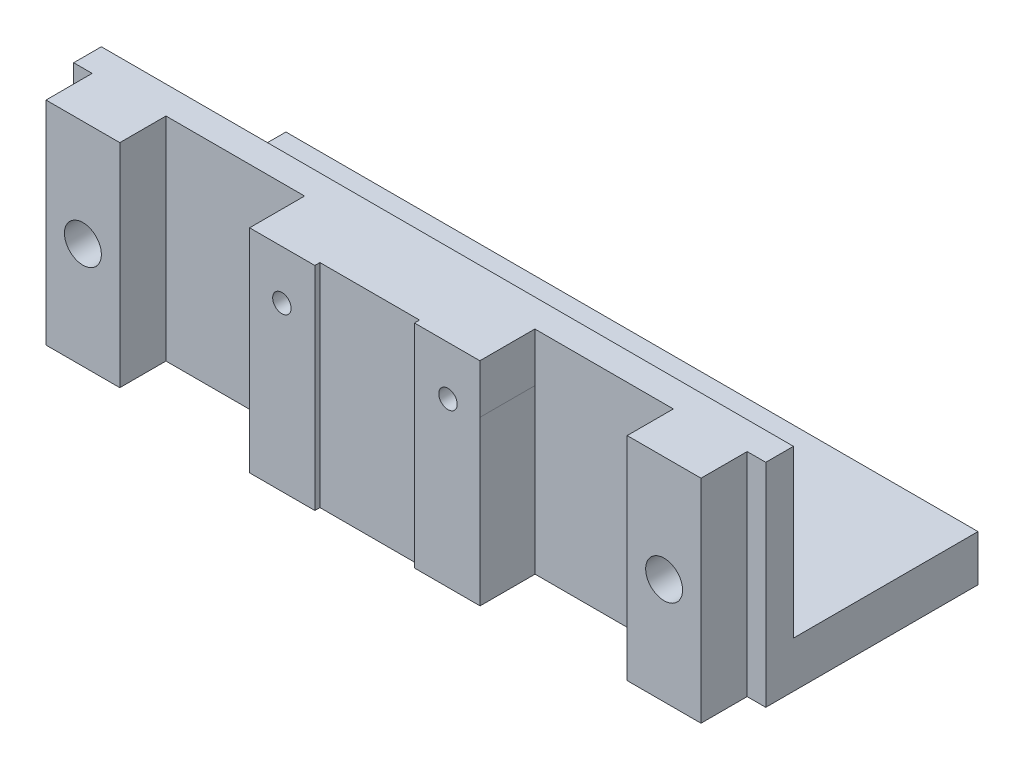
SolidWorks part; units mm, degrees
ref_plane "Front Plane" through (0, 0, 0) normal (0, 0, 1) x (1, 0, 0)
ref_plane "Top Plane" through (0, 0, 0) normal (0, 1, 0) x (1, 0, 0)
ref_plane "Right Plane" through (0, 0, 0) normal (1, 0, 0) x (0, 0, -1)
sketch "Sketch1" plane through (0, 0, 0) normal (0, 1, 0) x (1, 0, 0)
  line L1 (-25, -11.5) -> (25, -11.5)
  line L2 (-25, -11.5) -> (-25, 11.5)
  line L3 (-25, 11.5) -> (25, 11.5)
  line L4 (25, -11.5) -> (25, 11.5)
  line L5 (-25, -11.5) -> (25, 11.5) construction
  line L6 (-25, 11.5) -> (25, -11.5) construction
  point P0 (0, 0)
extrude "Boss-Extrude12" add sketch "Sketch1" along normal blind 3
sketch "Sketch17" plane through (0, 3, 0) normal (0, 1, 0) x (1, 0, 0)
  line L0 (25, -11.5) -> (25, 11.5) construction
  line L1 (-25, -11.5) -> (25, -11.5)
  line L2 (-25, -11.5) -> (-25, -8.5)
  line L3 (-25, -8.5) -> (25, -8.5)
  line L4 (25, -11.5) -> (25, -8.5)
extrude "Boss-Extrude13" add sketch "Sketch17" along normal blind 20
sketch "Sketch18" plane through (25, 0, 0) normal (1, 0, 0) x (0, 0, -1)
  line L0 (-11.5, 23) -> (-8.5, 23)
  line L1 (-8.5, 23) -> (-8.5, 3)
  line L2 (-8.5, 3) -> (11.5, 3)
  line L3 (11.5, 3) -> (11.5, 0)
  line L4 (11.5, 0) -> (-11.5, 0)
  line L5 (-11.5, 0) -> (-11.5, 23)
extrude "Boss-Extrude15" add sketch "Sketch18" along normal blind 25
sketch "Sketch19" plane through (0, 0, 0) normal (0, -1, 0) x (1, 0, 0)
  circle A0 centre (-7.5, -1.0693) radius 3
  circle A1 centre (12.5, -1.0693) radius 3
  circle A2 centre (32.5, -1.0693) radius 3
extrude "Cut-Extrude1" cut sketch "Sketch19" against normal blind 10
sketch "Sketch20" plane through (0, 0, 0) normal (0, -1, 0) x (1, 0, 0)
  circle A3 centre (-7.5, -1.0693) radius 3
  circle A4 centre (12.5, -1.0693) radius 3
  circle A5 centre (32.5, -1.0693) radius 3
  circle A6 centre (-7.5, -1.0693) radius 4
  circle A7 centre (12.5, -1.0693) radius 4
  circle A8 centre (32.5, -1.0693) radius 4
sketch "Sketch21" plane through (0, 0, 11.5) normal (0, 0, 1) x (1, 0, 0)
  line L1 (-25, 23) -> (50, 23) construction
  line L4 (0.0228, 17.6839) -> (0, 0)
  line L5 (0, 0) -> (25, 0)
  line L6 (0.0228, 17.6839) -> (0.0228, 23)
  line L7 (0.0228, 23) -> (24.9772, 23)
  line L8 (24.9772, 17.6839) -> (24.9772, 23)
  line L9 (24.9772, 17.6839) -> (25, 0)
  arc A0 (1.7156, 21.4339) -> (1.7156, 13.9339) centre (5.0228, 17.6839) ccw construction
extrude "Boss-Extrude17" add sketch "Sketch21" along normal blind 5.96
sketch "Sketch22" plane through (0, 23, 0) normal (0, 1, 0) x (1, 0, 0)
  line L0 (15.8929, -16.909) -> (17.8908, -16.909)
  line L1 (17.8908, -16.909) -> (17.8908, -17.46)
  line L2 (24.9772, -17.46) -> (0.0228, -17.46) construction
  line L3 (15.8929, -16.909) -> (9.0929, -16.909)
  line L4 (9.0929, -16.909) -> (7.0929, -16.909)
  line L5 (7.0929, -16.909) -> (7.0929, -17.46)
  line L6 (7.0929, -17.46) -> (17.8908, -17.46)
extrude "Cut-Extrude2" cut sketch "Sketch22" against normal through all
sketch "Sketch23" plane through (0, 0, 17.46) normal (0, 0, 1) x (1, 0, 0)
  circle A0 centre (3.5228, 17.6839) radius 1
  circle A1 centre (21.5228, 17.6839) radius 1
extrude "Cut-Extrude3" cut sketch "Sketch23" against normal through all
sketch "Sketch24" plane through (0, 0, 11.5) normal (0, 0, 1) x (1, 0, 0)
  line L1 (-25, 23) -> (0.0228, 23) construction
  line L2 (-23, 23) -> (-23, 0)
  line L3 (-25, 0) -> (0, 0) construction
  line L4 (-23, 0) -> (-15, 0)
  line L5 (-15, 0) -> (-15, 23)
  line L6 (-15, 23) -> (-23, 23)
  line L13 (39.9837, 23) -> (47.9837, 23)
  line L14 (39.9837, 0) -> (39.9837, 23)
  line L15 (47.9837, 0) -> (39.9837, 0)
  line L16 (47.9837, 23) -> (47.9837, 0)
extrude "Boss-Extrude20" add sketch "Sketch24" along normal blind 5
extrude "Boss-Extrude22" add sketch "Sketch20" along normal blind 3
sketch "Sketch25" plane through (0, 0, 16.5) normal (0, 0, 1) x (1, 0, 0)
  line L3 (12.4929, 23.1217) -> (12.4919, 0)
  line L4 (15.8929, 23.1217) -> (9.0929, 23.1217) construction
  line L5 (17.8908, 0) -> (7.0929, 0) construction
  circle A0 centre (-19, 11.5) radius 2
  circle A1 centre (43.9847, 11.4973) radius 2
extrude "Cut-Extrude4" cut sketch "Sketch25" against normal through all contours A1 | A0 region at (-19, 11.5, 16.5) region at (43.9847, 11.4973, 16.5)
sketch "Sketch26" plane through (0, 3, 0) normal (0, 1, 0) x (1, 0, 0)
  line L1 (-25, 11.5) -> (50, 11.5)
  line L2 (-25, 11.5) -> (-25, -8.5)
  line L3 (-25, -8.5) -> (50, -8.5)
  line L4 (50, 11.5) -> (50, -8.5)
extrude "Boss-Extrude23" add sketch "Sketch26" along normal blind 2
sketch "Sketch27" plane through (0, 3, 0) normal (0, -1, 0) x (1, 0, 0)
  circle A0 centre (-7.5, -1.0693) radius 3
  circle A1 centre (12.5, -1.0693) radius 3
  circle A2 centre (32.5, -1.0693) radius 3
extrude "Cut-Extrude5" cut sketch "Sketch27" against normal through all
